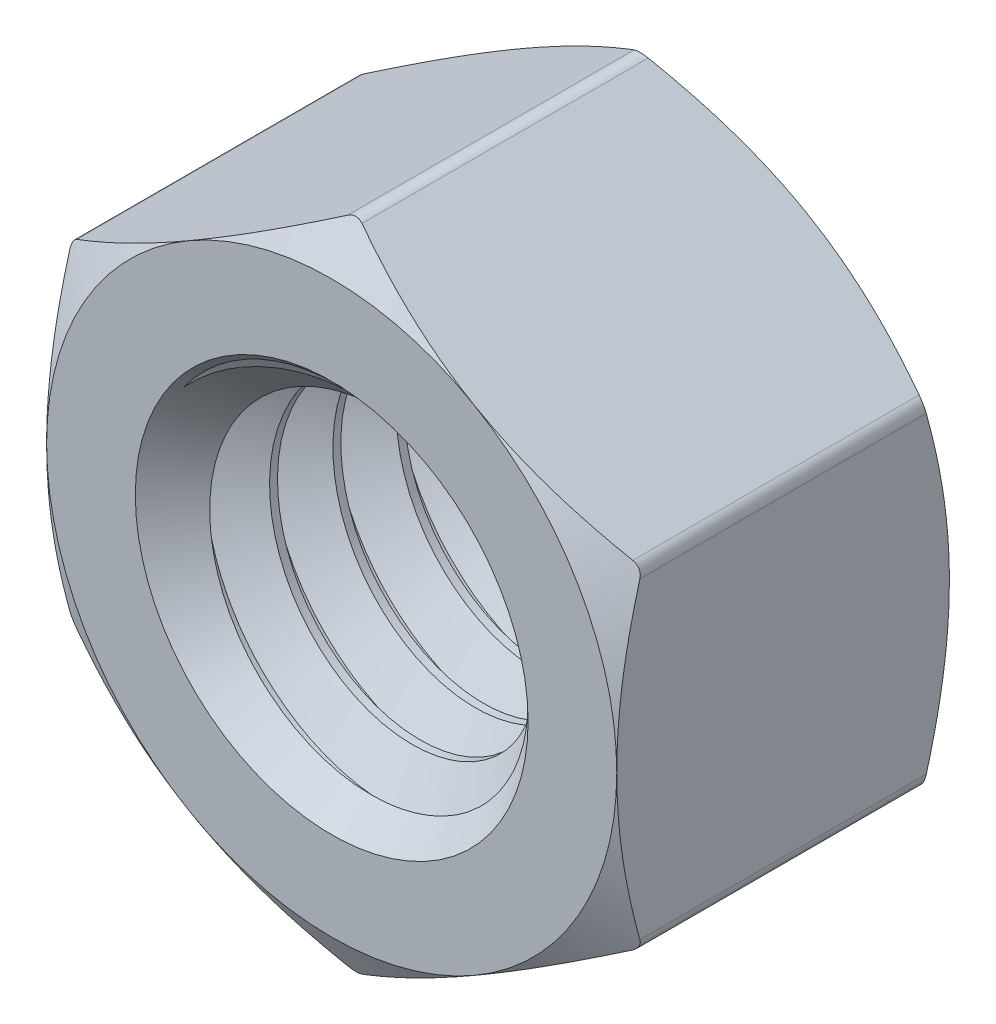
SolidWorks part; units mm, degrees
ref_plane "Front" through (0, 0, 0) normal (0, 0, 1) x (1, 0, 0)
ref_plane "Top" through (0, 0, 0) normal (0, 1, 0) x (1, 0, 0)
ref_plane "Right" through (0, 0, 0) normal (1, 0, 0) x (0, 0, -1)
sketch "Sketch1" plane through (0, 0, 0) normal (0, 0, 1) x (1, 0, 0)
  line L0 (0, 4.7625) -> (0, 3.175) construction
  line L1 (-7.1437, 4.1244) -> (-7.1437, -4.1244)
  line L2 (-7.1437, -4.1244) -> (0, -8.2489)
  line L3 (0, -8.2489) -> (7.1437, -4.1244)
  line L4 (7.1437, -4.1244) -> (7.1437, 4.1244)
  line L5 (7.1437, 4.1244) -> (0, 8.2489)
  line L6 (0, 8.2489) -> (-7.1437, 4.1244)
  circle A0 centre (0, 0) radius 7.1438 construction
  circle A1 centre (0, 0) radius 4.7625 construction
  point P10 (0, 4.7625)
  dimension "Width" = 14.2875
  dimension "Thread Size" = 9.525
  dimension "Thread Pitch" = 1.5875
sketch "Sketch2" plane through (0, 0, 0) normal (1, 0, 0) x (0, 0, -1)
  line L0 (-4.1672, 0) -> (4.1672, 0) construction
  line L1 (-4.1672, 8.2489) -> (4.1672, 8.2489) construction
  dimension "Height" = 8.3344
sketch "Sketch15" plane through (0, 0, 0) normal (0, 0, 1) x (1, 0, 0)
  line L1 (0, 8.2489) -> (-7.1437, 4.1244)
  line L2 (-7.1437, 4.1244) -> (-7.1438, -4.1244)
  line L3 (-7.1438, -4.1244) -> (0, -8.2489)
  line L4 (0, -8.2489) -> (7.1438, -4.1244)
  line L5 (7.1438, -4.1244) -> (7.1438, 4.1244)
  line L6 (7.1438, 4.1244) -> (0, 8.2489)
  circle A0 centre (0, 0) radius 7.1438 construction
extrude "Boss-Extrude2" add sketch "Sketch15" along normal mid plane 8.3344
sketch "Sketch16" plane through (0, 0, 0) normal (0, 0, 1) x (1, 0, 0)
  circle A0 centre (0, 0) radius 4.7625 construction
  circle A1 centre (0, 0) radius 4.7625
sketch "Sketch4" plane through (0, 0, -4.1672) normal (0, 0, -1) x (-1, 0, 0)
  circle A0 centre (0, 0) radius 4.7625 construction
  circle A1 centre (0, 0) radius 4.7625
extrude "Cut-Extrude4" cut sketch "Sketch16" against normal through all both and the other way through all
sketch "Sketch7" plane through (0, 0, 4.1672) normal (0, 0, 1) x (1, 0, 0)
  circle A0 centre (0, 0) radius 7.1438 construction
  circle A1 centre (0, 0) radius 7.1438
extrude "Cut-Extrude5" cut sketch "Sketch7" against normal through all draft 60 flip side to cut
mirror "Mirror4" about plane through (0, 0, 0) normal (0, 0, 1) of "Cut-Extrude5"
fillet "Fillet2" radius 0.3572 6 edges at (-7.1437, 4.1244, 0) (-7.1438, -4.1244, 0) (0, -8.2489, 0) (7.1438, -4.1244, 0) (7.1438, 4.1244, 0) (0, 8.2489, 0)
sketch "Sketch8" plane through (0, 0, 4.1672) normal (0, 0, 1) x (1, 0, 0)
  line L0 (1.2326, -4.6002) -> (0, 0) construction
  line L2 (0, 4.7625) -> (0, 3.175) construction
  circle A0 centre (0, 0) radius 4.7625 construction
  point P0 (1.2326, -4.6002)
  dimension "D1" = 15
sketch "Sketch13" plane through (0, 0, -4.1672) normal (0, 0, -1) x (-1, 0, 0)
  circle A0 centre (0, 0) radius 4.7625 construction
  circle A1 centre (0, 0) radius 4.7625
extrude "Boss-Extrude1" add sketch "Sketch13" against normal up to surface (8.3344 mm away) separate body up to face at (4.7625, 0, 4.1672)
curve "Helix/Spiral3" pitch 1.5875 height 9.9219 radius 4.7625 centre (0, 0, -4.1672) axis (0, 0, 1) start towards (0, 1, 0)
sketch "Sketch12" plane through (0, 0, 0) normal (1, 0, 0) x (0, 0, -1)
  line L0 (5.5562, 4.7625) -> (4.1672, 4.7625)
  line L1 (5.5562, 4.7625) -> (4.9609, 3.7314)
  line L2 (4.9609, 3.7314) -> (4.7625, 3.7314)
  line L3 (4.7625, 3.7314) -> (4.1672, 4.7625)
  line L4 (4.8617, 3.7314) -> (4.8617, 4.7625) construction
  line L5 (4.4648, 4.2469) -> (5.2586, 4.2469) construction
  dimension "D1" = 60
  dimension "D2" = 0.1984
  dimension "D3" = 0.7937
sweep "Cut-Sweep1" cut profiles "Sketch12" path "Helix/Spiral3" align with end faces yes
sketch "Sketch17" plane through (0, 0, 4.1672) normal (0, 0, 1) x (1, 0, 0)
  circle A1 centre (0, 0) radius 4.7625
  circle A2 centre (0, 0) radius 4.7625
  dimension "D1" = 0
extrude "Boss-Extrude3" add sketch "Sketch17" against normal up to surface (8.3344 mm away) up to face at (4.7625, 0, -4.1672)
combine bodies "Combine1" operation type subtract main body 127 bodies to subtract 118
sketch "Sketch10" plane through (0, 0, 4.1672) normal (0, 0, 1) x (1, 0, 0)
  circle A0 centre (0, 0) radius 4.7625 construction
  circle A1 centre (0, 0) radius 4.7625 construction
  circle A2 centre (0, 0) radius 4.9212
  dimension "D1" = 0.1588
extrude "Cut-Extrude2" cut sketch "Sketch10" against normal through all draft 45
sketch "Sketch11" plane through (0, 0, -4.1672) normal (0, 0, -1) x (-1, 0, 0)
  circle A1 centre (0, 0) radius 4.9212 construction
  circle A2 centre (0, 0) radius 4.9212
extrude "Cut-Extrude3" cut sketch "Sketch11" against normal through all draft 45
equation "\"D1\"= \"Height@Sketch2\""
equation "\"D3@Helix/Spiral3\"=\"Height@Sketch2\"+\"Thread Pitch@Sketch1\""
equation "\"D4@Helix/Spiral3\"=\"Thread Pitch@Sketch1\""
equation "\"D2@Sketch12\" = \"D4@Helix/Spiral3\"*.125"
equation "\"D3@Sketch12\" = \"D4@Helix/Spiral3\"*.50"
equation "\"D1@Boss-Extrude2\"=\"Height@Sketch2\""
equation "\"D1@Fillet2\"=\"Width@Sketch1\"*0.025"
equation "\"D1@Sketch10\"=\"Thread Pitch@Sketch1\"*0.1"
